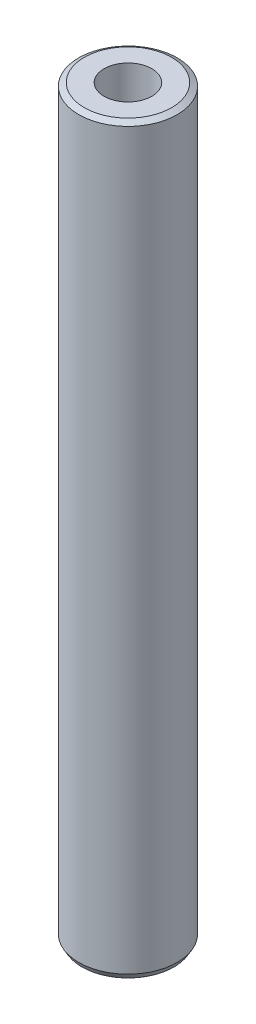
SolidWorks part; units mm, degrees
ref_plane "Front Plane" through (0, 0, 0) normal (0, 0, 1) x (1, 0, 0)
ref_plane "Top Plane" through (0, 0, 0) normal (0, 1, 0) x (1, 0, 0)
ref_plane "Right Plane" through (0, 0, 0) normal (1, 0, 0) x (0, 0, -1)
sketch "Sketch1" plane through (0, 0, 0) normal (0, 1, 0) x (1, 0, 0)
  circle A0 centre (0, 0) radius 37.5
  dimension "SHAFT_OD" = 75
extrude "Boss-Extrude1" add sketch "Sketch1" along normal blind 565.7409
sketch "Sketch2" plane through (0, 0, 0) normal (0, 1, 0) x (1, 0, 0)
  circle A0 centre (0, 0) radius 18.2049
  dimension "BORE_D" = 36.4099
extrude "Cut-Extrude1" cut sketch "Sketch2" along normal through all
chamfer "Chamfer1" distance 2.457 angle 60 2 edges at (0, 565.7409, 37.5) (0, 0, 37.5) first distance on face at (0, 565.7409, 37.5) first distance on face at (0, 0, 18.2049)
